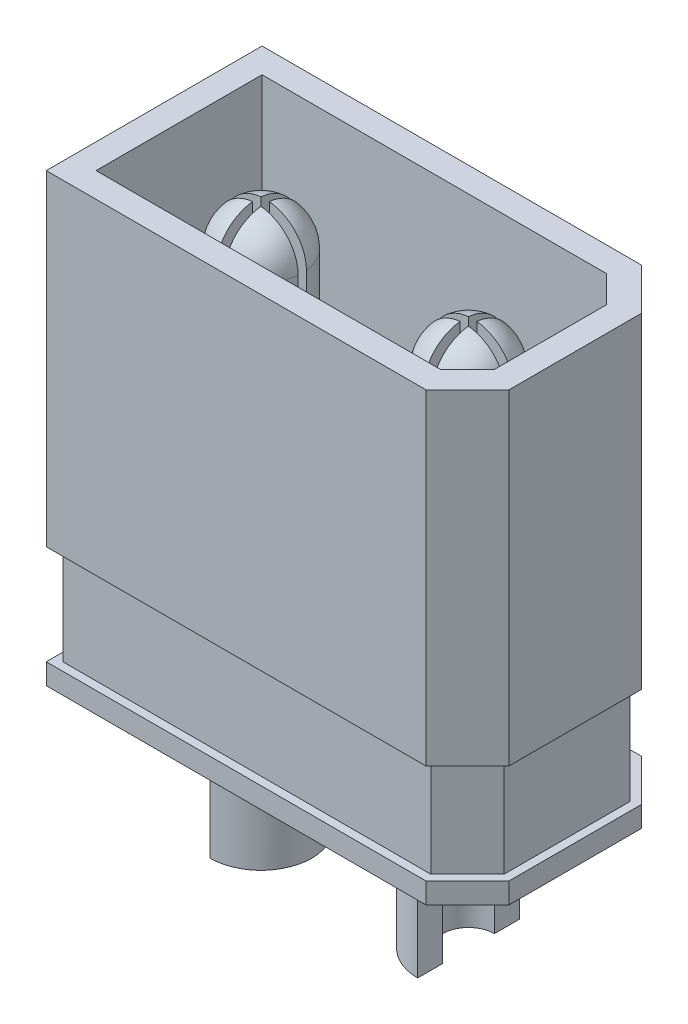
SolidWorks part; units mm, degrees
ref_plane "Front Plane" through (0, 0, 0) normal (0, 0, 1) x (1, 0, 0)
ref_plane "Top Plane" through (0, 0, 0) normal (0, 1, 0) x (1, 0, 0)
ref_plane "Right Plane" through (0, 0, 0) normal (1, 0, 0) x (0, 0, -1)
sketch "Sketch1" plane through (0, 0, 0) normal (0, 1, 0) x (1, 0, 0)
  line L0 (5.075, 1.6) -> (4.075, 2.6)
  line L1 (-5.075, 2.6) -> (5.075, 2.6)
  line L2 (-5.075, 2.6) -> (-5.075, -2.6)
  line L3 (-5.075, -2.6) -> (5.075, -2.6)
  line L4 (5.075, 2.6) -> (5.075, -2.6)
  line L5 (-5.075, 2.6) -> (5.075, -2.6) construction
  line L6 (-5.075, -2.6) -> (5.075, 2.6) construction
  line L7 (-5.075, 0) -> (5.075, 0) construction
  line L8 (5.075, -1.6) -> (4.075, -2.6)
  point P0 (0, 0)
  dimension "D1" = 5.2
  dimension "D2" = 10.15
  dimension "D3" = 1
  dimension "D4" = 45
extrude "Shape" add sketch "Sketch1" along normal blind 10.75 contours L8 L4 L0 L1 L2 L3 region at (-0.0916, 0, 0)
sketch "Sketch2" plane through (0, 10.75, 0) normal (0, 1, 0) x (1, 0, 0)
  line L12 (3.8265, -2) -> (4.475, -1.3515)
  line L13 (4.475, -1.3515) -> (4.475, 1.3515)
  line L14 (4.475, 1.3515) -> (3.8265, 2)
  line L15 (3.8265, 2) -> (-4.475, 2)
  line L16 (-4.475, 2) -> (-4.475, -2)
  line L17 (-4.475, -2) -> (3.8265, -2)
  line L18 (3.8265, -2) -> (4.475, -1.3515)
  line L19 (4.475, -1.3515) -> (4.475, 1.3515)
  line L20 (4.475, 1.3515) -> (3.8265, 2)
  line L21 (3.8265, 2) -> (-4.475, 2)
  line L22 (-4.475, 2) -> (-4.475, -2)
  line L23 (-4.475, -2) -> (3.8265, -2)
  dimension "D1" = 0.6
extrude "Cut-Extrude1" cut sketch "Sketch2" against normal blind 6.75
sketch "Sketch3" plane through (0, 4, 0) normal (0, 1, 0) x (1, 0, 0)
  line L0 (-4.475, 0) -> (4.475, 0) construction
  line L1 (-4.475, 2) -> (-4.475, -2) construction
  line L2 (4.475, -1.3515) -> (4.475, 1.3515) construction
  line L3 (0, 2) -> (0, -2) construction
  line L4 (3.8265, 2) -> (-4.475, 2) construction
  line L5 (-4.475, -2) -> (3.8265, -2) construction
  line L7 (1.6754, -1.6) -> (-1.6754, -1.6)
  line L8 (1.6754, -1.6) -> (1.6754, 1.6)
  line L9 (1.6754, 1.6) -> (-1.6754, 1.6)
  line L10 (-1.6754, -1.6) -> (-1.6754, 1.6)
  line L11 (1.6754, -1.6) -> (-1.6754, 1.6) construction
  line L12 (1.6754, 1.6) -> (-1.6754, -1.6) construction
  circle A0 centre (-2.5, 0) radius 1.8
  circle A1 centre (2.5, 0) radius 1.8
  point P15 (0, 0)
  point P22 (0, 0)
  dimension "D2" = 3.6
  dimension "D1" = 5
  dimension "D3" = 3.2
extrude "Cut-Extrude2" cut sketch "Sketch3" against normal up to next contours L7 A1 L9 A0 region at (0, 4, 0)
fillet "Fillet1" radius 0.2 4 edges at (-1.6754, 2, 1.6) (1.6754, 2, 1.6) (1.6754, 2, -1.6) (-1.6754, 2, -1.6)
sketch "Sketch4" plane through (0, 4, 0) normal (0, 1, 0) x (1, 0, 0)
  line L0 (0, 2) -> (0, -2) construction
  line L13 (-4.475, 2) -> (3.8265, 2) construction
  line L14 (-4.475, -2) -> (3.8265, -2) construction
  circle A0 centre (-2.5, 0) radius 1
  circle A2 centre (2.5, 0) radius 1
  dimension "D1" = 2
extrude "Boss-Extrude2" add sketch "Sketch4" along normal offset from surface (6.1 mm away) 0.65 contours A0 | A0 | A0 | A0 | A2 | A2 | A2 | A2 region at (-2.5, 4, 0) region at (2.5, 4, 0) up to face at (1.2755, 10.75, 0)
fillet "Fillet2" radius 1 2 edges at (2.5, 10.1, 1) (-2.5, 10.1, 1)
sketch "Sketch5" plane through (0, 10.75, 0) normal (0, 1, 0) x (1, 0, 0)
  line L0 (0, 2.6) -> (0, -2.6) construction
  line L1 (-2.6, 1) -> (-2.4, 1)
  line L2 (-2.6, 1) -> (-2.6, -1)
  line L3 (-2.6, -1) -> (-2.4, -1)
  line L4 (-2.4, 1) -> (-2.4, -1)
  line L5 (-2.6, 1) -> (-2.4, -1) construction
  line L6 (-2.6, -1) -> (-2.4, 1) construction
  line L7 (-1.5, 0.1) -> (-3.5, 0.1)
  line L8 (-1.5, 0.1) -> (-1.5, -0.1)
  line L9 (-1.5, -0.1) -> (-3.5, -0.1)
  line L10 (-3.5, 0.1) -> (-3.5, -0.1)
  line L11 (-1.5, 0.1) -> (-3.5, -0.1) construction
  line L12 (-1.5, -0.1) -> (-3.5, 0.1) construction
  line L13 (-5.075, 2.6) -> (4.075, 2.6) construction
  line L14 (-5.075, -2.6) -> (4.075, -2.6) construction
  line L15 (1.5, 0.1) -> (1.5, -0.1)
  line L16 (1.5, -0.1) -> (3.5, -0.1)
  line L17 (3.5, 0.1) -> (3.5, -0.1)
  line L18 (1.5, 0.1) -> (3.5, 0.1)
  line L19 (2.6, 1) -> (2.4, 1)
  line L20 (2.4, 1) -> (2.4, -1)
  line L21 (2.6, -1) -> (2.4, -1)
  line L22 (2.6, 1) -> (2.6, -1)
  circle A0 centre (-2.5, 0) radius 1 construction
  point P0 (-2.5, 0)
  point P8 (-2.5, 0)
  dimension "D1" = 0.2
extrude "Cut-Extrude3" cut sketch "Sketch5" against normal up to surface (6.75 mm away) contours L4 L3 L2 L1 | L7 L10 L9 L8 | L16 L17 L18 L15 | L20 L21 L22 L19 up to face at (2.5, 4, 1)
ref_plane "Plane1" through (0, 0.5, 0) normal (0, -1, 0) x (-1, 0, 0)
sketch "Sketch6" plane through (0, 0.5, 0) normal (0, -1, 0) x (-1, 0, 0)
  line L13 (-4.875, -1.5172) -> (-3.9922, -2.4)
  line L14 (-3.9922, -2.4) -> (4.875, -2.4)
  line L15 (4.875, -2.4) -> (4.875, 2.4)
  line L16 (4.875, 2.4) -> (-3.9922, 2.4)
  line L17 (-3.9922, 2.4) -> (-4.875, 1.5172)
  line L18 (-4.875, 1.5172) -> (-4.875, -1.5172)
  line L19 (-4.875, -1.5172) -> (-3.9922, -2.4)
  line L20 (-3.9922, -2.4) -> (4.875, -2.4)
  line L21 (4.875, -2.4) -> (4.875, 2.4)
  line L22 (4.875, 2.4) -> (-3.9922, 2.4)
  line L23 (-3.9922, 2.4) -> (-4.875, 1.5172)
  line L24 (-4.875, 1.5172) -> (-4.875, -1.5172)
  line L25 (-5.075, -1.6) -> (-4.075, -2.6)
  line L26 (-4.075, -2.6) -> (5.075, -2.6)
  line L27 (5.075, -2.6) -> (5.075, 2.6)
  line L28 (5.075, 2.6) -> (-4.075, 2.6)
  line L29 (-4.075, 2.6) -> (-5.075, 1.6)
  line L30 (-5.075, 1.6) -> (-5.075, -1.6)
  line L31 (-5.075, -1.6) -> (-4.075, -2.6)
  line L32 (-4.075, -2.6) -> (5.075, -2.6)
  line L33 (5.075, -2.6) -> (5.075, 2.6)
  line L34 (5.075, 2.6) -> (-4.075, 2.6)
  line L35 (-4.075, 2.6) -> (-5.075, 1.6)
  line L36 (-5.075, 1.6) -> (-5.075, -1.6)
  dimension "D1" = 0.2
  dimension "D2" = 0
extrude "Cut-Extrude4" cut sketch "Sketch6" against normal blind 2.4
sketch "Sketch8" plane through (0, 0, 0) normal (0, -1, 0) x (1, 0, 0)
  line L7 (-4.475, -2) -> (-4.475, 2) construction
  line L8 (3.8265, -2) -> (-4.475, -2) construction
  line L9 (4.475, -1.3515) -> (3.8265, -2) construction
  line L10 (4.475, 1.3515) -> (4.475, -1.3515) construction
  line L11 (3.8265, 2) -> (4.475, 1.3515) construction
  line L12 (-4.475, 2) -> (3.8265, 2) construction
  line L13 (-4.475, -2) -> (-4.475, 2)
  line L14 (3.8265, -2) -> (-4.475, -2)
  line L15 (4.475, -1.3515) -> (3.8265, -2)
  line L16 (4.475, 1.3515) -> (4.475, -1.3515)
  line L17 (3.8265, 2) -> (4.475, 1.3515)
  line L24 (-4.475, 2) -> (3.8265, 2)
extrude "Cut-Extrude5" cut sketch "Sketch8" against normal blind 1
sketch "Sketch7" plane through (0, 1, 0) normal (0, -1, 0) x (1, 0, 0)
  line L0 (0, 1.6) -> (0, -1.6) construction
  line L1 (-1.0717, 1.6) -> (1.0717, 1.6) construction
  line L2 (-1.0717, -1.6) -> (1.0717, -1.6) construction
  circle A0 centre (-2.5, 0) radius 1.225
  arc A1 (-2.4, -0.995) -> (-1.505, -0.1) centre (-2.5, 0) ccw construction
  circle A2 centre (-2.5, 0) radius 0.625
  circle A3 centre (2.5, 0) radius 0.625
  circle A4 centre (2.5, 0) radius 1.225
  dimension "D1" = 0.6
  dimension "D2" = 2.45
extrude "Boss-Extrude3" add sketch "Sketch7" along normal blind 4
sketch "Sketch9" plane through (0, -3, 0) normal (0, -1, 0) x (1, 0, 0)
  line L0 (0, 1.6) -> (0, -1.6) construction
  line L1 (-2.5, 1.225) -> (-3.725, 1.225)
  line L2 (-2.5, 1.225) -> (-2.5, -1.225)
  line L3 (-2.5, -1.225) -> (-3.725, -1.225)
  line L4 (-3.725, 1.225) -> (-3.725, -1.225)
  line L5 (-1.0717, 1.6) -> (1.0717, 1.6) construction
  line L6 (-1.0717, -1.6) -> (1.0717, -1.6) construction
  line L7 (-2.5, 1.225) -> (-2.5, -1.225) construction
  line L8 (2.5, 1.225) -> (3.725, 1.225)
  line L9 (2.5, 1.225) -> (2.5, -1.225)
  line L10 (2.5, -1.225) -> (3.725, -1.225)
  line L11 (3.725, 1.225) -> (3.725, -1.225)
  circle A0 centre (-2.5, 0) radius 1.225 construction
  circle A1 centre (-2.5, 0) radius 1.225 construction
extrude "Cut-Extrude6" cut sketch "Sketch9" against normal blind 2.3
